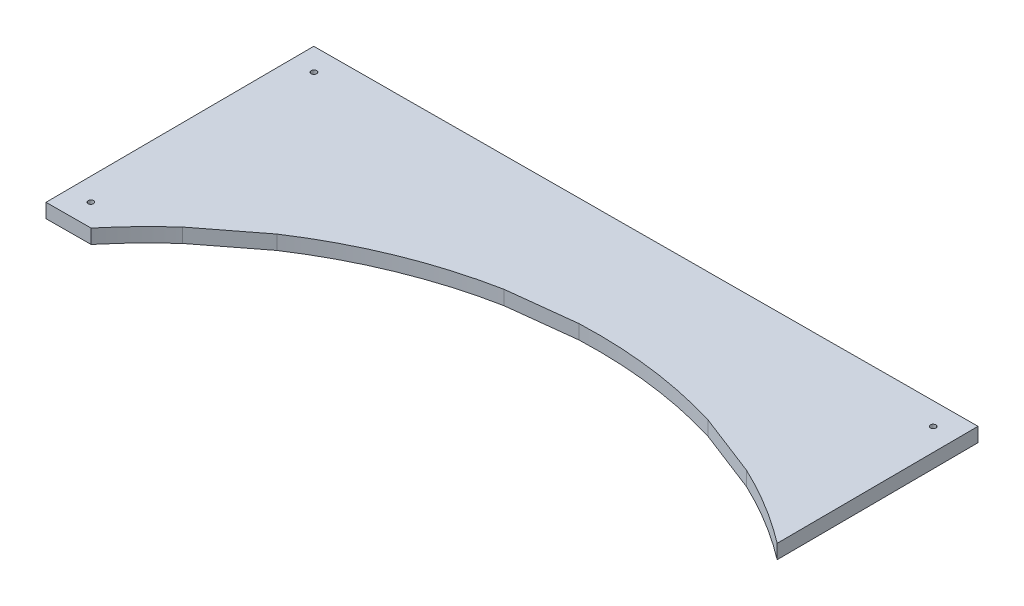
SolidWorks part; units mm, degrees
material "Balsa"
ref_plane "Front Plane" through (0, 0, 0) normal (0, 0, 1) x (1, 0, 0)
ref_plane "Top Plane" through (0, 0, 0) normal (0, 1, 0) x (1, 0, 0)
ref_plane "Right Plane" through (0, 0, 0) normal (1, 0, 0) x (0, 0, -1)
sketch "Sketch1" plane through (0, 0, 0) normal (0, 1, 0) x (1, 0, 0)
  line L0 (19.9998, 0.0912) -> (0, 0)
  line L5 (0, 0) -> (-0.5473, 119.9988)
  line L6 (-0.5473, 119.9988) -> (294.4497, 121.3441)
  line L7 (294.4497, 121.3441) -> (294.8601, 31.3441)
  line L17 (40.0057, 20.8844) -> (63.7564, 39.219)
  line L18 (135.7736, 68.5436) -> (165.7736, 72.0231)
  line L19 (231.7567, 63.5858) -> (259.7794, 52.7343)
  arc A0 (19.9998, 0.0912) -> (40.0057, 20.8844) centre (173.7506, -127.8177) cw
  arc A1 (63.7564, 39.219) -> (135.7736, 68.5436) centre (173.7506, -127.8177) cw
  arc A2 (165.7736, 72.0231) -> (231.7567, 63.5858) centre (173.7506, -127.8177) cw
  arc A3 (259.7794, 52.7343) -> (294.8601, 31.3441) centre (173.7506, -127.8177) cw
  circle A4 centre (9.4982, 110.0445) radius 1.225
  circle A5 centre (9.9543, 10.0455) radius 1.225
  circle A6 centre (284.4954, 111.2986) radius 1.225
  dimension "D5" = 200
  dimension "D8" = 2.45
  dimension "D11" = 2.45
  dimension "D14" = 2.45
  dimension "D1" = 295
  dimension "D2" = 20
  dimension "D3" = 120
  dimension "D4" = 90
  dimension "D6" = 10
  dimension "D7" = 10
  dimension "D9" = 10
  dimension "D10" = 10
  dimension "D12" = 10
  dimension "D13" = 10
extrude "Boss-Extrude1" add sketch "Sketch1" along normal blind 6.35
